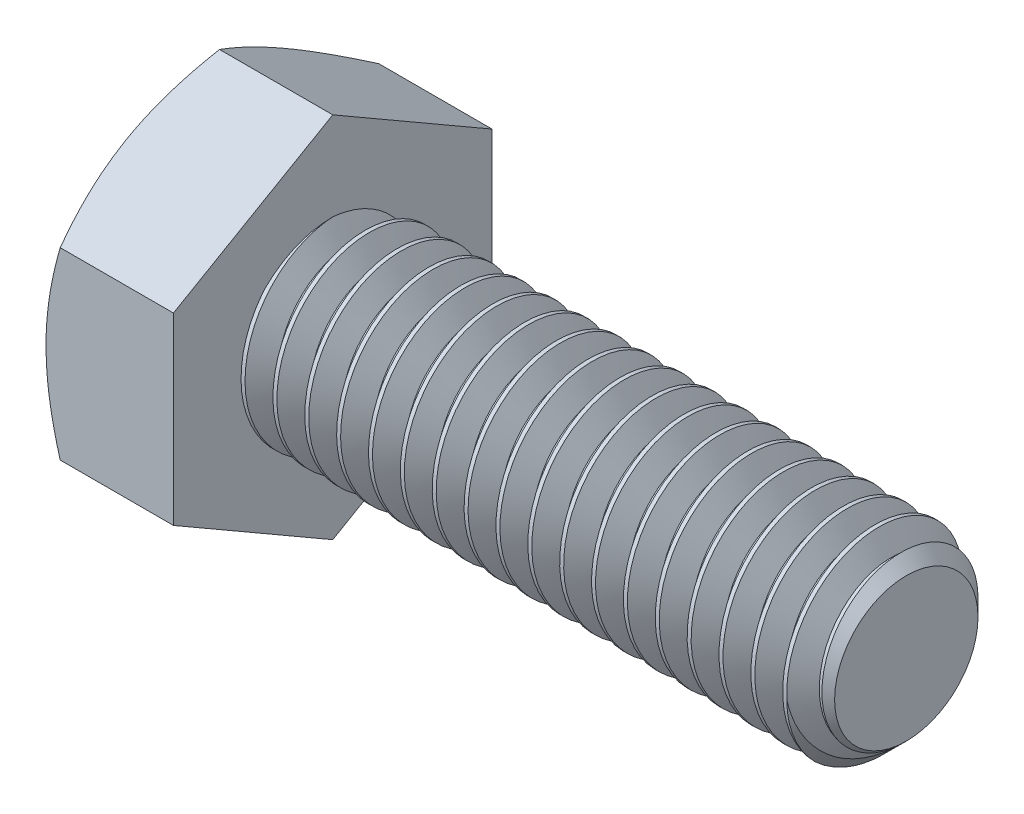
SolidWorks part; units mm, degrees
ref_plane "Front Plane" through (0, 0, 0) normal (0, 0, 1) x (1, 0, 0)
ref_plane "Top Plane" through (0, 0, 0) normal (0, 1, 0) x (1, 0, 0)
ref_plane "Right Plane" through (0, 0, 0) normal (1, 0, 0) x (0, 0, -1)
sketch "Sketch1" plane through (0, 0, 0) normal (0, 0, 1) x (1, 0, 0)
  line L0 (-11, 0) -> (11, 0) construction
  line L1 (-7, 5) -> (-7, -5) construction
  line L2 (-11, 5) -> (-11, -5) construction
  line L3 (11, 3) -> (11, -3) construction
  point P8 (7.5, -3)
  dimension "D1" = 3.5
  dimension "Thread Dia" = 6
  dimension "Hex" = 10
  dimension "Head Ht" = 4
  dimension "Length" = 18
ref_plane "Plane2" through (11, 0, 0) normal (1, 0, 0) x (0, 0, -1)
sketch "Sketch2" plane through (11, 0, 0) normal (1, 0, 0) x (0, 0, -1)
  circle A0 centre (0, 0) radius 3
extrude "Boss-Extrude1" add sketch "Sketch2" against normal up to vertex (18 mm away) up to point (-7, -5, 0)
sketch "Sketch4" plane through (11, 0, 0) normal (1, 0, 0) x (0, 0, -1)
  circle A1 centre (0, 0) radius 3
  circle A2 centre (0, 0) radius 3
  dimension "D1" = 0
curve "Helix/Spiral1" pitch 1 height 19 turns 19 parameters "Pitch"=1
chamfer "Chamfer1" distance 0.75 angle 45 1 edges at (11, 0, -3)
sketch "Sketch5" plane through (0, 0, 0) normal (0, 0, 1) x (1, 0, 0)
  line L0 (11, 3) -> (11.375, 2.3505)
  line L1 (11.375, 2.3505) -> (11.5, 2.3505)
  line L2 (11.5, 2.3505) -> (11.875, 3)
  line L3 (11, 3) -> (11.875, 3)
  line L4 (11.4375, 2.3505) -> (11.4375, 3) construction
  line L5 (11.1875, 2.6752) -> (11.6875, 2.6752) construction
  line L6 (11, -3) -> (11, 3) construction
  dimension "D1" = 60
  dimension "D2" = 0.125
  dimension "D3" = 0.5
sweep "Cut-Sweep1" cut profiles "Sketch5" path "Helix/Spiral1"
sketch "Sketch3" plane through (-7, 0, 0) normal (-1, 0, 0) x (0, 0, 1)
  line L0 (0, 5) -> (0, -5) construction
  line L1 (-5, -2.8868) -> (0, -5.7735)
  line L2 (0, -5.7735) -> (5, -2.8868)
  line L3 (5, -2.8868) -> (5, 2.8868)
  line L4 (5, 2.8868) -> (0, 5.7735)
  line L5 (0, 5.7735) -> (-5, 2.8868)
  line L6 (-5, 2.8868) -> (-5, -2.8868)
  circle A0 centre (0, 0) radius 5 construction
extrude "Boss-Extrude2" add sketch "Sketch3" along normal up to vertex (4 mm away) up to point (-11, -5, 0)
sketch "Sketch6" plane through (-11, 0, 0) normal (-1, 0, 0) x (0, 0, 1)
  circle A0 centre (0, 0) radius 5 construction
  circle A1 centre (0, 0) radius 5
extrude "Cut-Extrude1" cut sketch "Sketch6" against normal through all draft 60 flip side to cut
sketch "Sketch9" plane through (0, 0, 0) normal (0, 0, 1) x (1, 0, 0)
  line L0 (-7, 3) -> (-7, 0)
  line L1 (-7, 0) -> (-40, 0)
  line L2 (-40, 0) -> (-43, 3)
  line L3 (-43, 3) -> (-7, 3)
  line L4 (-11, 0) -> (11, 0) construction
  line L5 (-7, 5) -> (-7, -5) construction
  line L6 (11, 3) -> (11, -3) construction
  dimension "D1" = 45
  dimension "MinThreadLg" = 54
revolve "Revolve1" [suppressed] add sketch "Sketch9" angle 360 about L1
equation "\"D2@Sketch5\" = \"Pitch@Helix/Spiral1\"*.125"
equation "\"D3@Sketch5\" = \"Pitch@Helix/Spiral1\"*.50"
equation "\"D3@Helix/Spiral1\" = \"Length@Sketch1\"+\"Pitch@Helix/Spiral1\""
equation "\"D1@Chamfer1\" = \"Pitch@Helix/Spiral1\"*.750"
equation "\"D1@Sketch1\" = \"Pitch@Helix/Spiral1\"*3.50"
